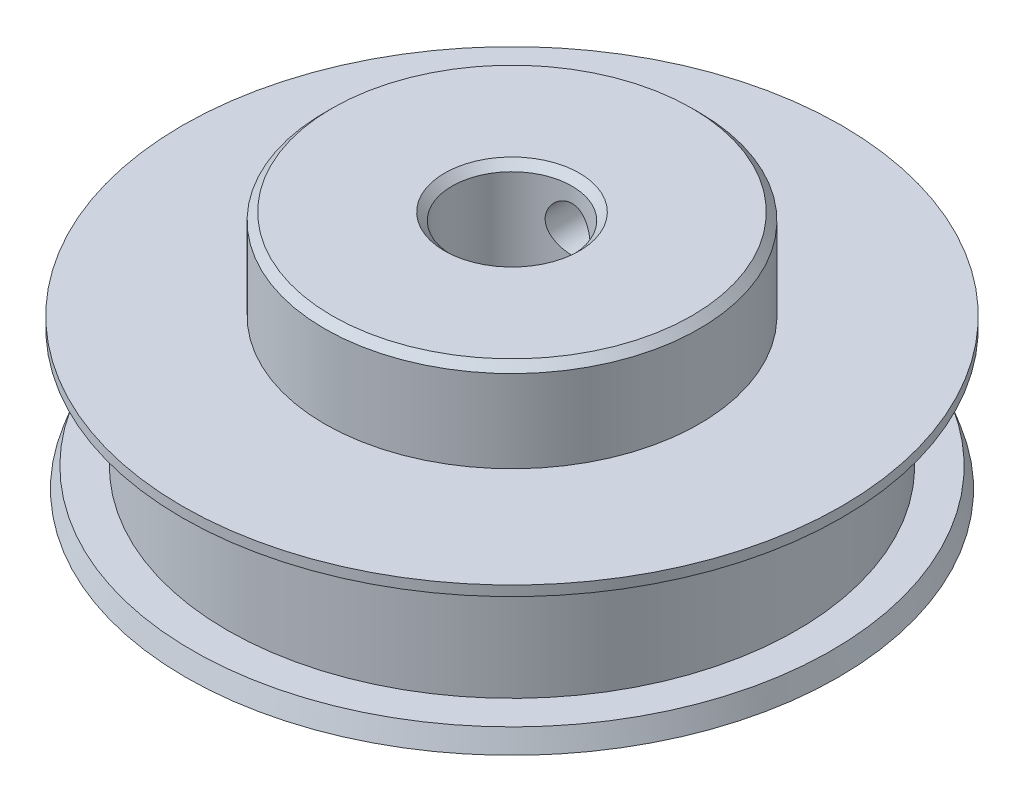
SolidWorks part; units mm, degrees
ref_plane "Front Plane" through (0, 0, 0) normal (0, 0, 1) x (1, 0, 0)
ref_plane "Top Plane" through (0, 0, 0) normal (0, 1, 0) x (1, 0, 0)
ref_plane "Right Plane" through (0, 0, 0) normal (1, 0, 0) x (0, 0, -1)
sketch "Sketch1" plane through (0, 0, 0) normal (0, 1, 0) x (1, 0, 0)
  circle A0 centre (0, 0) radius 22
  dimension "D1" = 44
extrude "Boss-Extrude1" add sketch "Sketch1" along normal blind 10
sketch "Sketch2" plane through (0, 10, 0) normal (0, 1, 0) x (1, 0, 0)
  circle A0 centre (0, 0) radius 12.5
  dimension "D1" = 25
extrude "Boss-Extrude2" add sketch "Sketch2" along normal blind 6
sketch "Sketch3" plane through (0, 0, 0) normal (0, 0, 1) x (1, 0, 0)
  line L0 (12.5, 16) -> (-12.5, 16) construction
  circle A0 centre (0, 13) radius 1.5
  point P4 (0, 0)
  dimension "D2" = 3
  dimension "D1" = 3
extrude "Cut-Extrude1" cut sketch "Sketch3" against normal up to next
sketch "Sketch4" plane through (0, 16, 0) normal (0, 1, 0) x (1, 0, 0)
  circle A0 centre (0, 0) radius 4
  dimension "D1" = 8
extrude "Cut-Extrude2" cut sketch "Sketch4" against normal up to next
sketch "Sketch5" plane through (0, 0, 0) normal (0, -1, 0) x (1, 0, 0)
  circle A0 centre (0, 0) radius 19
  circle A1 centre (0, 0) radius 22 construction
  circle A2 centre (0, 0) radius 22
  dimension "D1" = 38
extrude "Cut-Extrude3" cut sketch "Sketch5" against normal blind 7.3333 from offset 1.33 offset against normal yes
chamfer "Chamfer1" distance 0.666 distance2 2 2 edges at (0, 1.33, -22) (0, 8.6633, -22) first distance on face at (0, 1.33, -19) first distance on face at (0, 10, 22)
chamfer "Chamfer2" distance 0.5 3 edges at (0, 0, 4) (0, 16, 4) (0, 16, 12.5)
